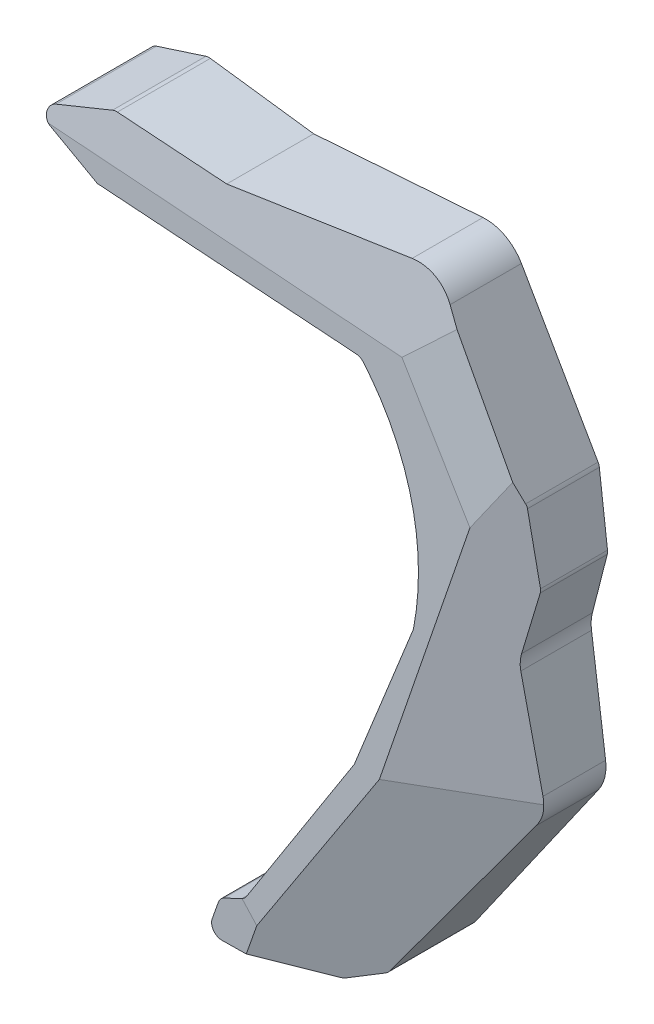
SolidWorks part; units mm, degrees
ref_plane "Front Plane" through (0, 0, 0) normal (0, 0, 1) x (1, 0, 0)
ref_plane "Top Plane" through (0, 0, 0) normal (0, 1, 0) x (1, 0, 0)
ref_plane "Right Plane" through (0, 0, 0) normal (1, 0, 0) x (0, 0, -1)
sketch "Sketch1" plane through (0, 0, 0) normal (0, 0, 1) x (1, 0, 0)
  line L0 (832.0122, 74.9833) -> (830.0516, 69.4431)
  line L1 (833.0861, 65.2092) -> (861.7465, 65.5827)
  line L2 (863.0915, 65.9012) -> (872.1968, 70.3209)
  line L3 (873.4105, 71.3552) -> (911.545, 125.7738)
  line L4 (913.7325, 134.7453) -> (909.3646, 167.411)
  line L5 (909.649, 172.2427) -> (914.2418, 190.1905)
  line L6 (914.3181, 191.3579) -> (911.7908, 212.3069)
  line L7 (911.3933, 213.5053) -> (887.6793, 254.884)
  line L8 (875.7552, 261.2369) -> (823.3703, 257.4929)
  line L9 (823.3703, 257.4929) -> (791.3915, 261.712)
  line L10 (790.0012, 261.5859) -> (774.7134, 256.6524)
  line L11 (774.0462, 250.9136) -> (788.1226, 242.4059)
  line L12 (788.1226, 242.4059) -> (863.9095, 232.407)
  line L13 (833.6188, 76.7803) -> (839.2873, 79.5319)
  line L14 (840.6182, 80.7459) -> (869.0186, 127.7362)
  line L15 (869.2944, 128.3193) -> (883.8849, 169.5478)
  arc A0 (865.901, 231.33) -> (884.0384, 170.1835) centre (806.8974, 180.5651) cw
  arc A1 (791.3915, 261.712) -> (790.0012, 261.5859) centre (790.9762, 258.5643) ccw
  arc A2 (911.7908, 212.3069) -> (911.3933, 213.5053) centre (908.6386, 211.9266) ccw
  arc A3 (914.2418, 190.1905) -> (914.3181, 191.3579) centre (911.1659, 190.9777) ccw
  arc A4 (872.1968, 70.3209) -> (873.4105, 71.3552) centre (870.8104, 73.1772) ccw
  arc A5 (861.7465, 65.5827) -> (863.0915, 65.9012) centre (861.7051, 68.7574) ccw
  arc A6 (839.2873, 79.5319) -> (840.6182, 80.7459) centre (837.9009, 82.3882) ccw
  arc A7 (830.0516, 69.4431) -> (833.0861, 65.2092) centre (833.0447, 68.3839) ccw
  arc A8 (832.0122, 74.9833) -> (833.6188, 76.7803) centre (835.0053, 73.924) cw
  arc A9 (869.0186, 127.7362) -> (869.2944, 128.3193) centre (866.3013, 129.3785) ccw
  arc A10 (883.8849, 169.5478) -> (884.0384, 170.1835) centre (880.8918, 170.607) ccw
  arc A11 (863.9095, 232.407) -> (865.901, 231.33) centre (863.4942, 229.2593) cw
  arc A12 (774.7134, 256.6524) -> (774.0462, 250.9136) centre (775.6885, 253.6308) ccw
  arc A13 (909.3646, 167.411) -> (909.649, 172.2427) centre (921.9525, 169.0942) cw
  arc A14 (911.545, 125.7738) -> (913.7325, 134.7453) centre (901.1445, 133.0621) ccw
  arc A15 (887.6793, 254.884) -> (875.7552, 261.2369) centre (876.6606, 248.5692) ccw
  dimension "D1" = 3.175
  dimension "D2" = 12.7
extrude "Boss-Extrude1" add sketch "Sketch1" along normal blind 19.05 and the other way blind 19.05 contours L7 A15 L8 L9 A1 L10 A12 L11 L12 A11 A0 A10 L15 A9 L14 A6 L13 A8 L0 A7 L1 A5 L2 A4 L3 A14 L4 A13 L5 A3 L6 A2
sketch "Sketch2" plane through (-1.943, 6.021, 0) normal (-0.3071, 0.9517, 0) x (0.9517, 0.3071, 0)
  line L0 (816.0951, 19.05) -> (816.0951, -19.05) construction
  line L1 (759.9129, -9.525) -> (859.3158, -9.525) construction
  point P0 (816.0951, -12.7)
  dimension "D1" = 3.175
sketch "Sketch3" plane through (44.9185, 340.4603, 0) normal (-0.1308, -0.9914, 0) x (0.9914, -0.1308, 0)
  line L0 (826.0882, -19.05) -> (826.0882, 19.05) construction
  line L1 (831.7151, 4.5049) -> (783.6342, 9.525) construction
  point P0 (826.0882, 8.2847)
  dimension "D1" = 3.175
ref_plane "Plane1" through (5.1547, 4.6894, 78.3831) normal (0.0655, 0.0596, 0.9961) x (0.9979, -0.0039, -0.0654)
sketch "Sketch4" plane through (5.1547, 4.6894, 78.3831) normal (0.0655, 0.0596, 0.9961) x (0.9979, -0.0039, -0.0654)
  line L1 (749.7917, 278.6271) -> (936.1714, 278.6271)
  line L2 (749.7917, 278.6271) -> (749.7917, 45.3412)
  line L3 (749.7917, 45.3412) -> (936.1714, 45.3412)
  line L4 (936.1714, 278.6271) -> (936.1714, 45.3412)
extrude "Cut-Extrude1" cut sketch "Sketch4" along normal through all
sketch "Sketch5" plane through (5.1547, 4.6894, 78.3831) normal (0.0655, 0.0596, 0.9961) x (0.9979, -0.0039, -0.0654)
  line L0 (784.7131, 248.255) -> (873.3802, 236.598)
sketch "Sketch6" plane through (47.478, 359.86, 0) normal (0.1308, 0.9914, 0) x (0.9914, -0.1308, 0)
  line L1 (782.616, 19.05) -> (782.616, -9.4499) construction
  point P0 (782.616, -7.8624)
  dimension "D1" = 1.5875
ref_plane "Plane2" through (9.762, 21.7169, 118.2914) normal (0.0809, 0.18, 0.9803) x (0.9954, -0.0662, -0.07)
sketch "Sketch7" plane through (9.762, 21.7169, 118.2914) normal (0.0809, 0.18, 0.9803) x (0.9954, -0.0662, -0.07)
  line L1 (708.7984, 305.7891) -> (940.7492, 305.7891)
  line L2 (708.7984, 305.7891) -> (708.7984, 84.1114)
  line L3 (708.7984, 84.1114) -> (940.7492, 84.1114)
  line L4 (940.7492, 305.7891) -> (940.7492, 84.1114)
extrude "Cut-Extrude2" cut sketch "Sketch7" along normal through all
sketch "Sketch8" plane through (5.1547, 4.6894, 78.3831) normal (0.0655, 0.0596, 0.9961) x (0.9979, -0.0039, -0.0654)
  line L0 (873.5909, 236.5703) -> (896.8137, 199.6568)
  line L1 (896.2099, 233.5966) -> (769.8949, 250.2031) construction
sketch "Sketch10" plane through (923.9562, 111.468, 0) normal (0.9928, 0.1198, 0) x (0, 0, -1)
  line L1 (19.05, 101.5701) -> (-6.3384, 101.5701) construction
  point P0 (-4.7509, 101.5701)
  dimension "D1" = 1.5875
ref_plane "Plane4" through (23.5492, 17.7166, 158.4861) normal (0.1461, 0.1099, 0.9831) x (0.9885, -0.0542, -0.1408)
sketch "Sketch11" plane through (23.5492, 17.7166, 158.4861) normal (0.1461, 0.1099, 0.9831) x (0.9885, -0.0542, -0.1408)
  line L1 (722.7568, 281.5652) -> (896.5709, 281.5652)
  line L2 (722.7568, 281.5652) -> (722.7568, 32.7154)
  line L3 (722.7568, 32.7154) -> (896.5709, 32.7154)
  line L4 (896.5709, 281.5652) -> (896.5709, 32.7154)
extrude "Cut-Extrude4" cut sketch "Sketch11" along normal through all
sketch "Sketch12" plane through (5.1547, 4.6894, 78.3831) normal (0.0655, 0.0596, 0.9961) x (0.9979, -0.0039, -0.0654)
  line L0 (895.3185, 202.0336) -> (872.7512, 124.7339)
  line L1 (908.7955, 180.6115) -> (873.5909, 236.5703) construction
sketch "Sketch13" plane through (915.3831, 122.4007, 0) normal (0.9912, 0.1325, 0) x (0, 0, -1)
  line L0 (19.05, 45.411) -> (-9.1839, 45.411) construction
  point P0 (-2.8339, 45.411)
  dimension "D1" = 6.35
ref_plane "Plane5" through (106.6065, -8.1056, 291.5179) normal (0.3433, -0.0261, 0.9389) x (0.9392, 0.0195, -0.3429)
sketch "Sketch14" plane through (106.6065, -8.1056, 291.5179) normal (0.3433, -0.0261, 0.9389) x (0.9392, 0.0195, -0.3429)
  line L1 (903.7331, 250.9378) -> (707.6032, 250.9378)
  line L2 (903.7331, 250.9378) -> (903.7331, 25.3183)
  line L3 (903.7331, 25.3183) -> (707.6032, 25.3183)
  line L4 (707.6032, 250.9378) -> (707.6032, 25.3183)
extrude "Cut-Extrude5" cut sketch "Sketch14" along normal through all
sketch "Sketch15" plane through (5.1547, 4.6894, 78.3831) normal (0.0655, 0.0596, 0.9961) x (0.9979, -0.0039, -0.0654)
  line L0 (873.2224, 126.348) -> (834.8357, 64.0208)
  line L1 (895.3185, 202.0336) -> (855.1107, 64.31) construction
  line L2 (829.7961, 63.9551) -> (848.76, 64.2024) construction
sketch "Sketch16" plane through (138.6941, -285.727, 0) normal (0.4367, -0.8996, 0) x (0.8996, 0.4367, 0)
  line L0 (805.2291, -19.05) -> (805.2291, 16.9332) construction
  point P0 (805.2291, 10.5832)
  dimension "D1" = 6.35
ref_plane "Plane6" through (107.8831, -38.088, 283.7544) normal (0.3526, -0.1245, 0.9275) x (0.9358, 0.0469, -0.3495)
sketch "Sketch17" plane through (107.8831, -38.088, 283.7544) normal (0.3526, -0.1245, 0.9275) x (0.9358, 0.0469, -0.3495)
  line L1 (719.745, 195.1976) -> (896.5641, 195.1976)
  line L2 (719.745, 195.1976) -> (719.745, 10.3538)
  line L3 (719.745, 10.3538) -> (896.5641, 10.3538)
  line L4 (896.5641, 195.1976) -> (896.5641, 10.3538)
extrude "Cut-Extrude6" cut sketch "Sketch17" along normal through all
